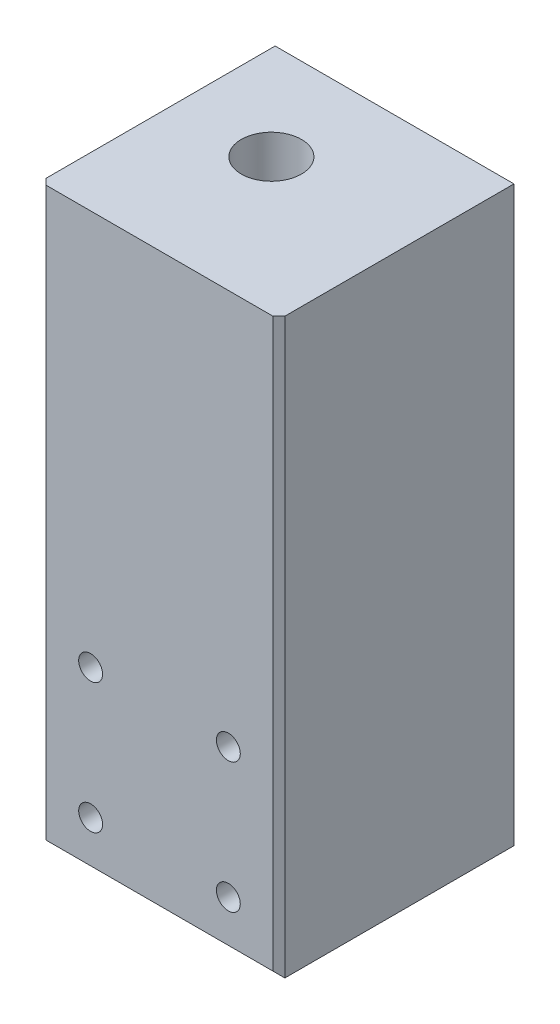
SolidWorks part; units mm, degrees
note: The reader was unsure of these and kept them because the rebuilt part matched: shared geometry of "Sketch3<2>", "Sketch4<4>".
material "McMaster 6061-T6"
ref_plane "Front" through (0, 0, 0) normal (0, 0, 1) x (1, 0, 0)
ref_plane "Top" through (0, 0, 0) normal (0, 1, 0) x (1, 0, 0)
ref_plane "Right" through (0, 0, 0) normal (1, 0, 0) x (0, 0, -1)
sketch "Sketch1" plane through (0, 0, 0) normal (0, 1, 0) x (1, 0, 0)
  line B0 (145.625, 87.9) -> (79.625, 87.9)
  line B1 (79.625, 87.9) -> (79.625, 25.4)
  line B2 (79.625, 25.4) -> (-125.375, 25.4)
  line B3 (-125.375, 25.4) -> (-125.375, 87.9)
  line B4 (-125.375, 87.9) -> (-145.625, 87.9)
  line B5 (-145.625, 87.9) -> (-145.625, 0)
  line B6 (-145.625, 0) -> (145.625, 0)
  line B7 (145.625, 0) -> (145.625, 87.9)
sketch_block_instance "Block-TopSection Base-1"
sketch_block "Block-TopSection Base" parameters "D1"=25.4
sketch "Sketch2" plane through (0, 0, 0) normal (0, 0, 1) x (1, 0, 0)
  line L0 (-125.375, 0) -> (-125.375, 60)
  line L1 (-145.625, 60) -> (-188.875, 60)
  line L2 (-188.875, 60) -> (-188.875, 0)
  line L3 (-188.875, 0) -> (-145.625, 0)
  line L4 (-188.875, 60) -> (-188.875, 152.4)
  line L5 (-188.875, 152.4) -> (-125.375, 152.4)
  line L6 (-125.375, 152.4) -> (-125.375, 60)
  line B0 (145.625, 0) -> (-145.625, 0)
  line B1 (145.625, 0) -> (145.625, 60)
  line B2 (145.625, 60) -> (-145.625, 60)
  line B3 (-145.625, 0) -> (-145.625, 60)
  arc B4 (101.925, 7) -> (95.325, 7) centre (98.625, 7) ccw
  arc B5 (95.325, 7) -> (101.925, 7) centre (98.625, 7) ccw
  arc B6 (82.325, 7) -> (88.925, 7) centre (85.625, 7) ccw
  arc B7 (88.925, 7) -> (82.325, 7) centre (85.625, 7) ccw
  arc B8 (82.325, 53) -> (88.925, 53) centre (85.625, 53) ccw
  arc B9 (88.925, 53) -> (82.325, 53) centre (85.625, 53) ccw
  arc B10 (95.325, 53) -> (101.925, 53) centre (98.625, 53) ccw
  arc B11 (101.925, 53) -> (95.325, 53) centre (98.625, 53) ccw
  circle B12 centre (139.275, 23.675) radius 1.5875
  circle B13 centre (113.875, 23.675) radius 1.5875
  circle B14 centre (113.875, 36.325) radius 1.5875
  circle B15 centre (139.275, 36.325) radius 1.5875
  arc B16 (-112.875, 31.75) -> (-112.875, 28.25) centre (-112.875, 30) ccw
  arc B17 (-112.875, 28.25) -> (-112.875, 31.75) centre (-112.875, 30) ccw
  arc B18 (-52.875, 31.75) -> (-52.875, 28.25) centre (-52.875, 30) ccw
  arc B19 (-52.875, 28.25) -> (-52.875, 31.75) centre (-52.875, 30) ccw
  arc B20 (7.125, 31.75) -> (7.125, 28.25) centre (7.125, 30) ccw
  arc B21 (7.125, 28.25) -> (7.125, 31.75) centre (7.125, 30) ccw
  arc B22 (67.125, 31.75) -> (67.125, 28.25) centre (67.125, 30) ccw
  arc B23 (67.125, 28.25) -> (67.125, 31.75) centre (67.125, 30) ccw
  arc B24 (-138.925, 7) -> (-132.325, 7) centre (-135.625, 7) ccw
  arc B25 (-132.325, 7) -> (-138.925, 7) centre (-135.625, 7) ccw
  arc B26 (-138.925, 53) -> (-132.325, 53) centre (-135.625, 53) ccw
  arc B27 (-132.325, 53) -> (-138.925, 53) centre (-135.625, 53) ccw
  dimension "D1" = 63.5
  dimension "D2" = 152.4
sketch_block_instance "Block-RightSection Side-1"
sketch_block "Block-RightSection Side"
extrude "Primary Extrusion" add sketch "Sketch2" along normal up to vertex from vertex contours B3 B0 L0 B2 B27 B26 B25 B24 | B24 B25 | B26 B27 | L3 B3 L1 L2 | B2 L6 L5 L4 L1
sketch "Sketch3" plane through (0, 0, -25.4) normal (0, 0, 1) x (1, 0, 0)
  line L0 (-145.625, 0) -> (145.625, 0) construction
  line L1 (-145.625, 60) -> (-125.375, 60) construction
  line L2 (-145.625, 60) -> (-145.625, 0) construction
  line L3 (-145.625, 0) -> (-125.375, 0) construction
  line L4 (-125.375, 60) -> (-125.375, 0) construction
  line L5 (-138.8158, 60) -> (-138.8158, 0) construction
  line L6 (145.625, 60) -> (79.625, 60) construction
  line L7 (145.625, 60) -> (145.625, 0) construction
  line L8 (145.625, 0) -> (79.625, 0) construction
  line L9 (79.625, 60) -> (79.625, 0) construction
  line L10 (-138.8158, 47.3) -> (145.625, 47.3) construction
  line L11 (79.625, 60) -> (145.625, 0) construction
  line L12 (145.625, 60) -> (79.625, 0) construction
  line L13 (-125.375, 60) -> (-188.875, 0) construction
  line L14 (-125.375, 0) -> (-188.875, 60) construction
  line L15 (-125.375, 60) -> (-188.875, 60) construction
  line L16 (-125.375, 0) -> (-188.875, 0) construction
  circle A0 centre (-138.8158, 47.3) radius 3.175
  circle A1 centre (-138.8158, 12.7) radius 3.175
  circle A2 centre (93.595, 47.3) radius 3.175
  circle A3 centre (131.655, 47.3) radius 3.175
  circle A4 centre (131.655, 12.7) radius 3.175
  circle A5 centre (93.595, 12.7) radius 3.175
  circle A6 centre (-175.4342, 47.3) radius 3.175
  circle A7 centre (-175.4342, 12.7) radius 3.175
  point P20 (93.595, 47.3)
  point P22 (131.655, 47.3)
  dimension "D1" = 6.35
  dimension "D2" = 12.7
  dimension "D3" = 12.7
extrude "Cut-Extrude2" cut sketch "Sketch3" against normal blind 25.4
extrude "Cut-Extrude3" cut sketch "Sketch3<2>" along normal blind 6.35 from surface at -62.5 contours A0 | A1 starting at face at (-157.125, 76.2, -87.9)
sketch "Sketch3<2>" plane through (0, 0, -25.4) normal (0, 0, 1) x (1, 0, 0) same geometry as "Sketch3"
chamfer "Chamfer1" distance 1.5875 angle 45 3 edges at (-157.125, 0, -25.4) (-125.375, 76.2, -25.4) (-188.875, 76.2, -25.4)
sketch "Sketch4" plane through (0, 0, 0) normal (0, -1, 0) x (1, 0, 0)
  line B0 (145.625, -87.9) -> (145.625, -26.9875)
  line B1 (145.625, -26.9875) -> (79.625, -26.9875)
  line B2 (79.625, -26.9875) -> (79.625, -87.9)
  line B3 (79.625, -87.9) -> (145.625, -87.9)
  line B4 (-125.375, -87.9) -> (-125.375, -26.9875)
  line B5 (-125.375, -26.9875) -> (-188.875, -26.9875)
  line B6 (-188.875, -26.9875) -> (-188.875, -87.9)
  line B7 (-188.875, -87.9) -> (-125.375, -87.9)
  line B8 (100.625, -48.6335) -> (100.625, -75.1665)
  line B9 (140.625, -75.1665) -> (140.625, -48.6335)
  line B10 (-143.875, -75.1665) -> (-143.875, -48.6335)
  line B11 (-183.875, -48.6335) -> (-183.875, -75.1665)
  arc B12 (140.625, -48.6335) -> (100.625, -48.6335) centre (120.625, -61.9) ccw
  arc B13 (100.625, -75.1665) -> (140.625, -75.1665) centre (120.625, -61.9) ccw
  arc B14 (123.375, -42.9) -> (117.875, -42.9) centre (120.625, -42.9) ccw
  arc B15 (117.875, -42.9) -> (123.375, -42.9) centre (120.625, -42.9) ccw
  arc B16 (104.44, -48.465) -> (109.94, -48.465) centre (107.19, -48.465) ccw
  arc B17 (109.94, -48.465) -> (104.44, -48.465) centre (107.19, -48.465) ccw
  arc B18 (136.81, -48.465) -> (131.31, -48.465) centre (134.06, -48.465) ccw
  arc B19 (131.31, -48.465) -> (136.81, -48.465) centre (134.06, -48.465) ccw
  arc B20 (104.44, -75.335) -> (109.94, -75.335) centre (107.19, -75.335) ccw
  arc B21 (109.94, -75.335) -> (104.44, -75.335) centre (107.19, -75.335) ccw
  arc B22 (117.875, -80.9) -> (123.375, -80.9) centre (120.625, -80.9) ccw
  arc B23 (123.375, -80.9) -> (117.875, -80.9) centre (120.625, -80.9) ccw
  arc B24 (131.31, -75.335) -> (136.81, -75.335) centre (134.06, -75.335) ccw
  arc B25 (136.81, -75.335) -> (131.31, -75.335) centre (134.06, -75.335) ccw
  arc B26 (112.625, -61.9) -> (128.625, -61.9) centre (120.625, -61.9) ccw
  arc B27 (128.625, -61.9) -> (112.625, -61.9) centre (120.625, -61.9) ccw
  arc B28 (-153.19, -75.335) -> (-147.69, -75.335) centre (-150.44, -75.335) ccw
  arc B29 (-147.69, -75.335) -> (-153.19, -75.335) centre (-150.44, -75.335) ccw
  arc B30 (-166.625, -80.9) -> (-161.125, -80.9) centre (-163.875, -80.9) ccw
  arc B31 (-161.125, -80.9) -> (-166.625, -80.9) centre (-163.875, -80.9) ccw
  arc B32 (-180.06, -48.465) -> (-174.56, -48.465) centre (-177.31, -48.465) ccw
  arc B33 (-174.56, -48.465) -> (-180.06, -48.465) centre (-177.31, -48.465) ccw
  arc B34 (-166.625, -42.9) -> (-161.125, -42.9) centre (-163.875, -42.9) ccw
  arc B35 (-161.125, -42.9) -> (-166.625, -42.9) centre (-163.875, -42.9) ccw
  arc B36 (-153.19, -48.465) -> (-147.69, -48.465) centre (-150.44, -48.465) ccw
  arc B37 (-147.69, -48.465) -> (-153.19, -48.465) centre (-150.44, -48.465) ccw
  arc B38 (-171.875, -61.9) -> (-155.875, -61.9) centre (-163.875, -61.9) ccw
  arc B39 (-155.875, -61.9) -> (-171.875, -61.9) centre (-163.875, -61.9) ccw
  arc B40 (-180.06, -75.335) -> (-174.56, -75.335) centre (-177.31, -75.335) ccw
  arc B41 (-174.56, -75.335) -> (-180.06, -75.335) centre (-177.31, -75.335) ccw
  arc B42 (-183.875, -75.1665) -> (-143.875, -75.1665) centre (-163.875, -61.9) ccw
  arc B43 (-143.875, -48.6335) -> (-183.875, -48.6335) centre (-163.875, -61.9) ccw
sketch_block_instance "Block-ScrewSideView-1"
sketch_block "Block-ScrewSideView"
extrude "Cut-Extrude4" cut sketch "Sketch4" against normal blind 6.35 contours B28 B29 | B30 B31 | B40 B41 | B36 B37 | B34 B35 | B32 B33
extrude "Cut-Extrude5" cut sketch "Sketch4<4>" against normal through all contours B38 B39
sketch "Sketch4<4>" plane through (0, 0, 0) normal (0, -1, 0) x (1, 0, 0) same geometry as "Sketch4"
